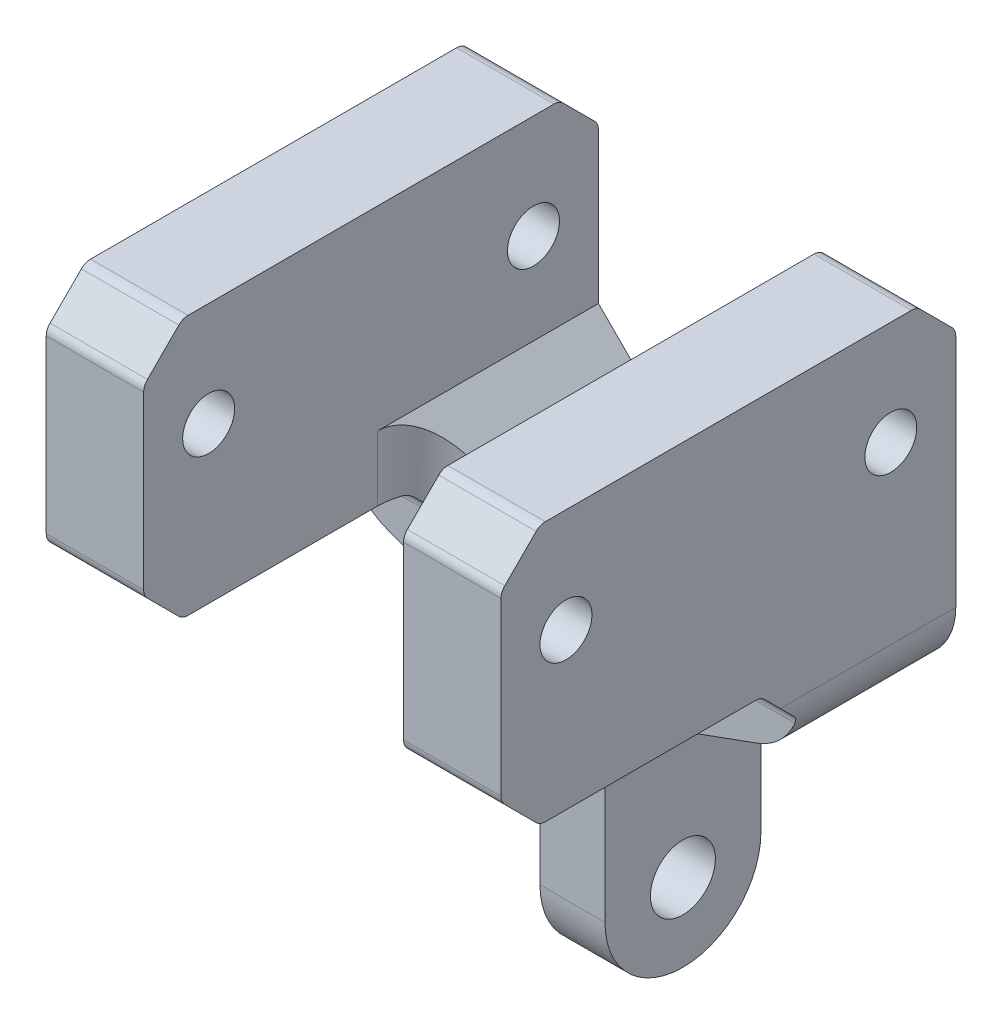
SolidWorks part; units mm, degrees
ref_plane "Front" through (0, 0, 0) normal (0, 0, 1) x (1, 0, 0)
ref_plane "Top" through (0, 0, 0) normal (0, 1, 0) x (1, 0, 0)
ref_plane "Right" through (0, 0, 0) normal (1, 0, 0) x (0, 0, -1)
sketch "Sketch1" plane through (0, 0, 0) normal (1, 0, 0) x (0, 0, -1)
  line L0 (0, 0) -> (-35, 0)
  line L1 (-35, 0) -> (-35, -20)
  line L2 (-35, -20) -> (-12, -20)
  line L3 (-12, -20) -> (-12, -50)
  line L4 (-12, -50) -> (0, -50)
  line L5 (0, -50) -> (0, 0)
  dimension "D1" = 35
  dimension "D2" = 20
  dimension "D3" = 50
  dimension "D4" = 12
extrude "Boss-Extrude1" add sketch "Sketch1" along normal mid plane 35
sketch "Sketch2" plane through (0, 0, 0) normal (0, 0, -1) x (-1, 0, 0)
  line L0 (17.5, -25) -> (2.5, -30.4596)
  line L1 (17.5, -50) -> (17.5, 0) construction
  line L2 (2.5, -30.4596) -> (2.5, -50)
  line L3 (-17.5, -50) -> (17.5, -50) construction
  line L4 (2.5, -50) -> (17.5, -50)
  line L5 (17.5, -50) -> (17.5, -25)
  line L6 (0, 12.1978) -> (0, -71.8602) construction
  line L7 (-17.5, -50) -> (-17.5, -25)
  line L8 (-2.5, -50) -> (-17.5, -50)
  line L9 (-2.5, -30.4596) -> (-2.5, -50)
  line L10 (-17.5, -25) -> (-2.5, -30.4596)
  line L11 (-17.5, 0) -> (17.5, 0) construction
  line L12 (10, -20) -> (-10, -20)
  line L13 (10, -20) -> (10, 0)
  line L14 (10, 0) -> (-10, 0)
  line L15 (-10, -20) -> (-10, 0)
  line L16 (10, -20) -> (-10, 0) construction
  line L17 (10, 0) -> (-10, -20) construction
  point P21 (0, -10)
  dimension "D1" = 5
  dimension "D2" = 110
  dimension "D3" = 5
  dimension "D4" = 20
  dimension "D5" = 20
extrude "Cut-Extrude1" cut sketch "Sketch2" against normal through all
sketch "Sketch3" plane through (-17.5, 0, 0) normal (-1, 0, 0) x (0, 0, 1)
  line L0 (17.5, 0) -> (17.5, -20) construction
  line L1 (0, 0) -> (35, 0) construction
  line L2 (35, -20) -> (12, -20) construction
  line L3 (35, 0) -> (35, -20) construction
  circle A0 centre (5, -8) radius 2
  circle A1 centre (30, -8) radius 2
  dimension "D1" = 4
  dimension "D2" = 5
  dimension "D3" = 8
extrude "Cut-Extrude2" cut sketch "Sketch3" against normal through all
chamfer "Chamfer1" distance 3 angle 45 8 edges at (13.75, -20, 35) (13.75, 0, 35) (-13.75, 0, 35) (-13.75, -20, 35) (13.75, -20, 12) (-13.75, -20, 12) (13.75, 0, 0) (-13.75, 0, 0)
chamfer "Chamfer2" distance 5 angle 45 2 edges at (10, -20, 6) (-10, -20, 6)
fillet "Fillet1" 2 edges at (0, -50, 12) (0, -50, 0) type full round first side face at (0, -26.6371, 12) second side face at (0, -20.9228, 0) middle face at (0, -50, 6)
sketch "Sketch4" plane through (2.5, 0, 0) normal (1, 0, 0) x (0, 0, -1)
  circle A0 centre (-6, -44) radius 2.5
  dimension "D1" = 5
extrude "Cut-Extrude3" cut sketch "Sketch4" against normal blind 35
fillet "Fillet2" radius 5 6 edges at (10, -19, 12) (-10, -19, 12) (2.5, -30.4596, 6) (17.5, -25, 6) (-17.5, -25, 6) (-2.5, -30.4596, 6)
fillet "Fillet3" radius 1 16 edges at (11.1347, -23, 12) (13.5413, -20, 15) (13.75, -20, 32) (13.75, -17, 35) (13.75, 0, 32) (13.75, 0, 3) (13.75, -3, 0) (13.75, -3, 35) (-13.75, -20, 32) (-13.5413, -20, 15) (-11.1347, -23, 12) (-13.75, -3, 0) (-13.75, 0, 3) (-13.75, 0, 32) (-13.75, -3, 35) (-13.75, -17, 35)
